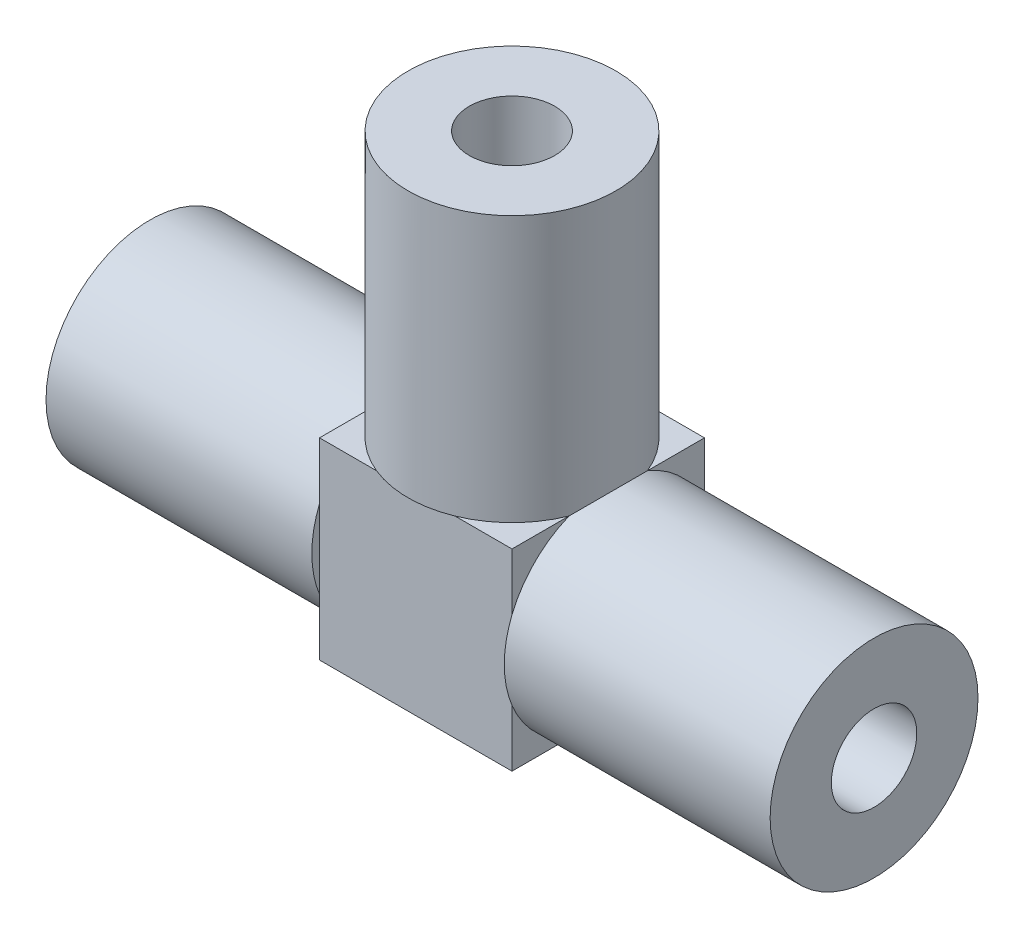
SolidWorks part; units mm, degrees
ref_plane "Front Plane" through (0, 0, 0) normal (0, 0, 1) x (1, 0, 0)
ref_plane "Top Plane" through (0, 0, 0) normal (0, 1, 0) x (1, 0, 0)
ref_plane "Right Plane" through (0, 0, 0) normal (1, 0, 0) x (0, 0, -1)
sketch "Block Sketch" plane through (0, 0, 0) normal (0, 0, 1) x (1, 0, 0)
  line L0 (-7.15, -7.15) -> (7.15, -7.15)
  line L1 (7.15, -7.15) -> (7.15, 7.15)
  line L2 (7.15, 7.15) -> (-7.15, 7.15)
  line L3 (-7.15, 7.15) -> (-7.15, -7.15)
extrude "Block" add sketch "Block Sketch" along normal mid plane 14.3
ref_axis "Engine Axis" through (29.59, 0, 0) along (-1, 0, 0)
ref_axis "Stem Axis" through (0, -9.4531, 0) along (0, 1, 0)
sketch "Arm X Sketch" plane through (0, 0, 0) normal (0, 0, 1) x (1, 0, 0)
  line L0 (-1000, 0) -> (1000, 0) construction
  line L1 (7.15, 0) -> (26.9, 0)
  line L2 (26.9, 0) -> (26.9, 7.722)
  line L3 (26.9, 7.722) -> (7.15, 7.722)
  line L4 (7.15, 7.722) -> (7.15, 0)
revolve "Arm X" add sketch "Arm X Sketch" angle 360 about L0
sketch "Arm Y Sketch" plane through (0, 0, 0) normal (0, 0, 1) x (1, 0, 0)
  line L0 (0, -500) -> (0, 500) construction
  line L1 (0, 7.15) -> (7.722, 7.15)
  line L2 (7.722, 7.15) -> (7.722, 26.9)
  line L3 (7.722, 26.9) -> (0, 26.9)
  line L4 (0, 26.9) -> (0, 7.15)
revolve "Arm Y" add sketch "Arm Y Sketch" angle 360 about L0
sketch "Socket X Sketch" plane through (0, 0, 0) normal (0, 0, 1) x (1, 0, 0)
  line L0 (-1000, 0) -> (1000, 0) construction
  line L1 (11.7, 0) -> (27.9, 0)
  line L2 (27.9, 0) -> (27.9, 3.175)
  line L3 (27.9, 3.175) -> (11.7, 3.175)
  line L4 (11.7, 3.175) -> (11.7, 0)
revolve "Socket X" cut sketch "Socket X Sketch" angle 360 about L0
sketch "Socket Y Sketch" plane through (0, 0, 0) normal (0, 0, 1) x (1, 0, 0)
  line L0 (0, -500) -> (0, 500) construction
  line L1 (0, 11.7) -> (3.175, 11.7)
  line L2 (3.175, 11.7) -> (3.175, 27.9)
  line L3 (3.175, 27.9) -> (0, 27.9)
  line L4 (0, 27.9) -> (0, 11.7)
revolve "Socket Y" cut sketch "Socket Y Sketch" angle 360 about L0
sketch "Arm -X Sketch" plane through (0, 0, 0) normal (0, 0, 1) x (1, 0, 0)
  line L0 (-1000, 0) -> (1000, 0) construction
  line L1 (-26.9, 0) -> (-7.15, 0)
  line L2 (-7.15, 0) -> (-7.15, 7.722)
  line L3 (-7.15, 7.722) -> (-26.9, 7.722)
  line L4 (-26.9, 7.722) -> (-26.9, 0)
revolve "Arm -X" add sketch "Arm -X Sketch" angle 360 about L0
sketch "Socket -X Sketch" plane through (0, 0, 0) normal (0, 0, 1) x (1, 0, 0)
  line L0 (-1000, 0) -> (1000, 0) construction
  line L1 (-27.9, 0) -> (-11.7, 0)
  line L2 (-11.7, 0) -> (-11.7, 3.175)
  line L3 (-11.7, 3.175) -> (-27.9, 3.175)
  line L4 (-27.9, 3.175) -> (-27.9, 0)
revolve "Socket -X" cut sketch "Socket -X Sketch" angle 360 about L0
